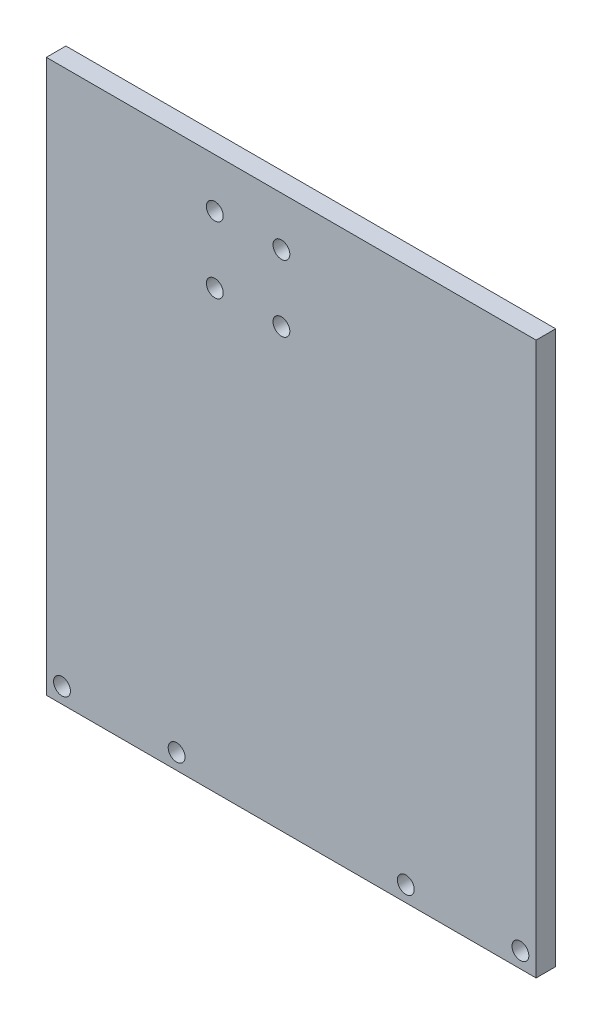
SolidWorks part; units mm, degrees
ref_plane "Front Plane" through (0, 0, 0) normal (0, 0, 1) x (1, 0, 0)
ref_plane "Top Plane" through (0, 0, 0) normal (0, 1, 0) x (1, 0, 0)
ref_plane "Right Plane" through (0, 0, 0) normal (1, 0, 0) x (0, 0, -1)
sketch "Sketch1" plane through (0, 0, 0) normal (0, 0, 1) x (1, 0, 0)
  line L0 (58.5, -66.5) -> (-58.5, -66.5) construction
  line L1 (-62.5, -70.5) -> (62.5, -70.5)
  line L2 (-62.5, -70.5) -> (-62.5, 70.5)
  line L3 (-62.5, 70.5) -> (62.5, 70.5)
  line L4 (62.5, -70.5) -> (62.5, 70.5)
  line L5 (-62.5, -70.5) -> (62.5, 70.5) construction
  line L6 (-62.5, 70.5) -> (62.5, -70.5) construction
  line L7 (-19.5, 41) -> (-2.5, 41) construction
  line L8 (-19.5, 41) -> (-19.5, 58) construction
  line L9 (-19.5, 58) -> (-2.5, 58) construction
  line L10 (-2.5, 41) -> (-2.5, 58) construction
  line L11 (-19.5, 41) -> (-2.5, 58) construction
  line L12 (-19.5, 58) -> (-2.5, 41) construction
  line L13 (62.5, -62.5) -> (-62.5, -62.5) construction
  line L14 (62.5, -62.5) -> (62.5, -70.5) construction
  line L15 (62.5, -70.5) -> (-62.5, -70.5) construction
  line L16 (-62.5, -62.5) -> (-62.5, -70.5) construction
  line L17 (62.5, -62.5) -> (-62.5, -70.5) construction
  line L18 (62.5, -70.5) -> (-62.5, -62.5) construction
  line L19 (29.25, -66.5) -> (-29.25, -66.5) construction
  line L20 (-58.5, -66.5) -> (-29.25, -66.5) construction
  line L21 (-29.25, -66.5) -> (0, -66.5) construction
  circle A0 centre (-19.5, 58) radius 2.15
  circle A1 centre (-2.5, 58) radius 2.15
  circle A2 centre (-2.5, 41) radius 2.15
  circle A3 centre (-19.5, 41) radius 2.15
  circle A4 centre (-58.5, -66.5) radius 4 construction
  circle A5 centre (-58.5, -66.5) radius 2.15
  circle A6 centre (58.5, -66.5) radius 2.15
  circle A7 centre (-29.25, -66.5) radius 2.15
  circle A8 centre (29.25, -66.5) radius 2.15
  point P0 (0, 0)
  point P6 (-11, 49.5)
  point P15 (0, -66.5)
  point P21 (0, -66.5)
  point P27 (0, -66.5)
  dimension "D3" = 4.3
  dimension "D2" = 12.5
  dimension "D1" = 125
  dimension "D4" = 17
  dimension "D5" = 65
  dimension "D6" = 120
  dimension "D7" = 8
extrude "Boss-Extrude1" add sketch "Sketch1" along normal mid plane 5
